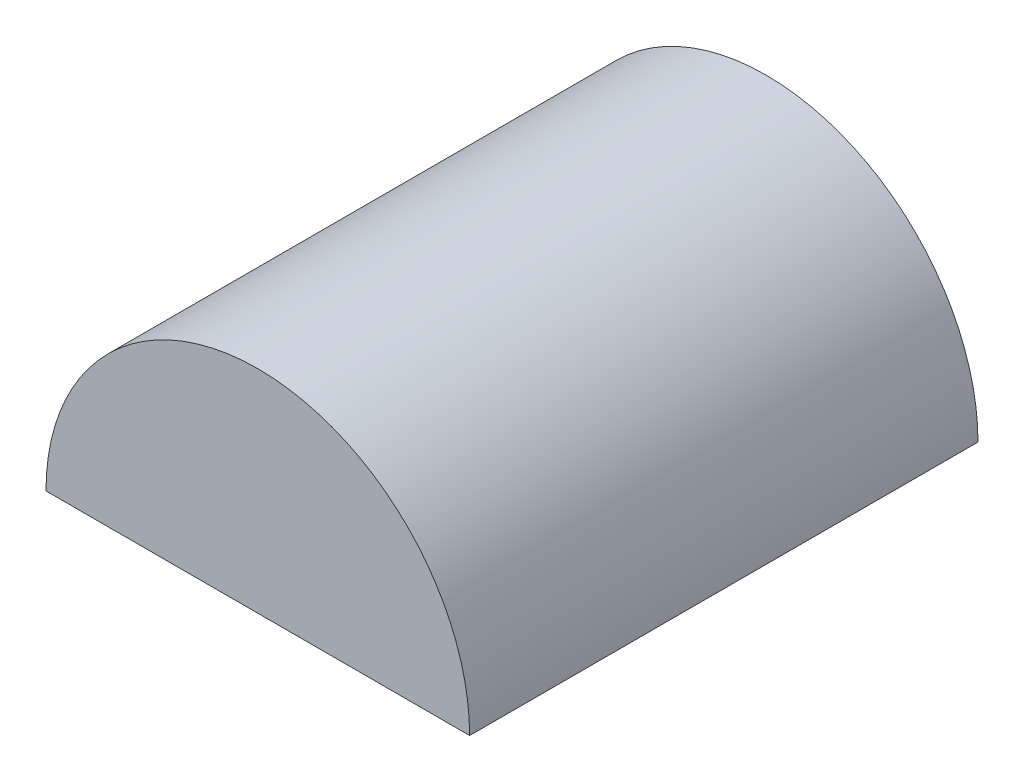
SolidWorks part; units mm, degrees
ref_plane "Front Plane" through (0, 0, 0) normal (0, 0, 1) x (1, 0, 0)
ref_plane "Top Plane" through (0, 0, 0) normal (0, 1, 0) x (1, 0, 0)
ref_plane "Right Plane" through (0, 0, 0) normal (1, 0, 0) x (0, 0, -1)
sketch "Sketch1" plane through (0, 0, 0) normal (0, 0, 1) x (1, 0, 0)
  line L0 (0, 0) -> (-0.25, 0)
  line L1 (0, 0) -> (0.25, 0)
  arc A0 (-0.25, 0) -> (0.25, 0) centre (0, 0) cw
  dimension "D1" = 0.25
extrude "Boss-Extrude1" add sketch "Sketch1" along normal blind 0.6
equation "\"t\"= 0.25'thickness of the sheets"
equation "\"t_cf\" = 0.115'thickness of single carbon fiber layer"
equation "\"t_kapton\" = 0.025'thickness of single Kapton flex layer"
equation "\"t_fr4\" = 0.1'thickness of FR4 with copper layer"
equation "\"joint_flex\"= 0.1'Width of flextures gap"
equation "\"joint_flex_eff\"= 0.02'Width of flecture after castelation"
equation "\"joint_fold\"= 0.2'Width of folding joints for 90deg fold"
equation "\"gap_tolerance\"= 0.002'Width to have interfecence fit between carbon fiber inserts"
equation "\"assemble_angle\"= 90'Angle of assembly parts"
equation "\"link_lift\"= 0.5'Actuation linkage amplification for the lift motion"
equation "\"link_swing\"= 0.45'Actuation linkage amplification for the swing motion"
equation "\"D1@Boss-Extrude1\"=\"joint_fold\""
equation "\"D1@Sketch1\"=\"t\""
